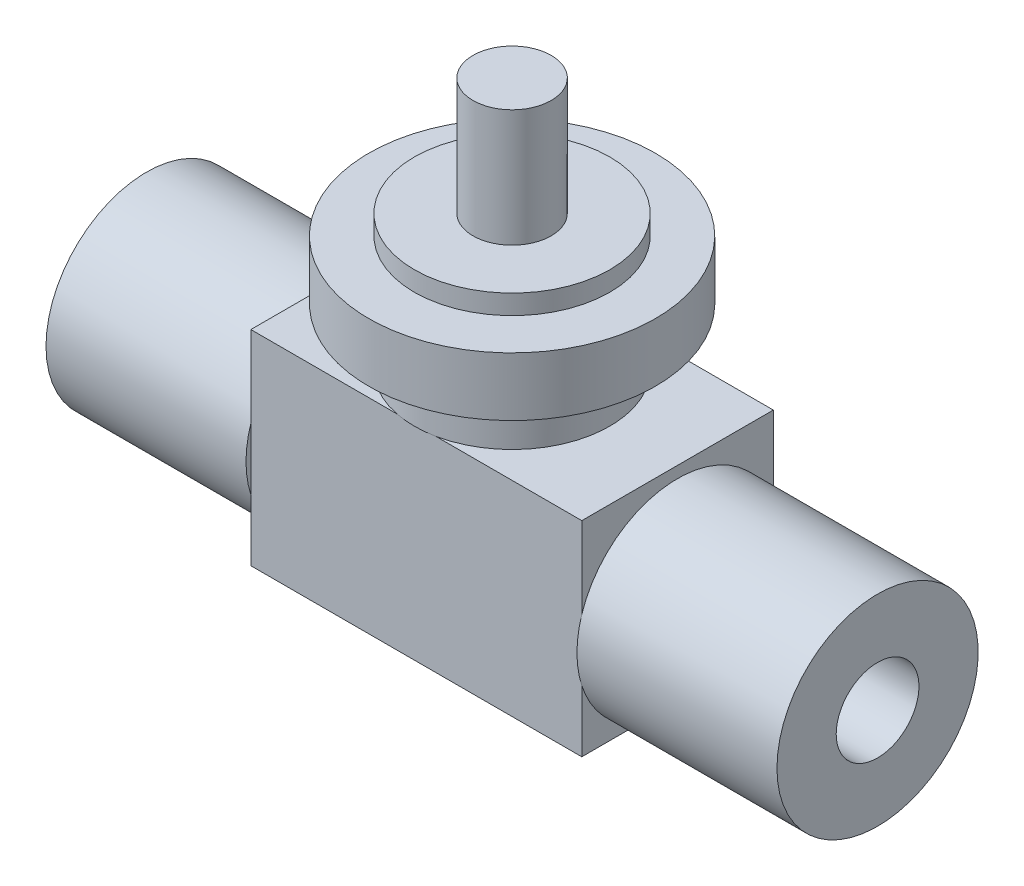
SolidWorks part; units mm, degrees
ref_plane "Front Plane" through (0, 0, 0) normal (0, 0, 1) x (1, 0, 0)
ref_plane "Top Plane" through (0, 0, 0) normal (0, 1, 0) x (1, 0, 0)
ref_plane "Right Plane" through (0, 0, 0) normal (1, 0, 0) x (0, 0, -1)
sketch "Body Sketch" plane through (0, 0, 0) normal (0, 0, 1) x (1, 0, 0)
  line L0 (-12.7, -7.1) -> (12.7, -7.1)
  line L1 (12.7, -7.1) -> (12.7, 8.6)
  line L2 (12.7, 8.6) -> (-12.7, 8.6)
  line L3 (-12.7, 8.6) -> (-12.7, -7.1)
extrude "Body" add sketch "Body Sketch" along normal mid plane 14.7
ref_axis "Engine Axis" through (30.855, 0, 0) along (-1, 0, 0)
ref_axis "Stem Axis" through (0, -9.5081, 0) along (0, 1, 0)
sketch "Nut +X Sketch" plane through (0, 0, 0) normal (0, 0, 1) x (1, 0, 0)
  line L0 (-1000, 0) -> (1000, 0) construction
  line L1 (12.7, 0) -> (28.05, 0)
  line L2 (28.05, 0) -> (28.05, 7.722)
  line L3 (28.05, 7.722) -> (12.7, 7.722)
  line L4 (12.7, 7.722) -> (12.7, 0)
revolve "Nut +X" add sketch "Nut +X Sketch" angle 360 about L0
sketch "Nut -X Sketch" plane through (0, 0, 0) normal (0, 0, 1) x (1, 0, 0)
  line L0 (-1000, 0) -> (1000, 0) construction
  line L1 (-28.05, 0) -> (-12.7, 0)
  line L2 (-12.7, 0) -> (-12.7, 7.722)
  line L3 (-12.7, 7.722) -> (-28.05, 7.722)
  line L4 (-28.05, 7.722) -> (-28.05, 0)
revolve "Nut -X" add sketch "Nut -X Sketch" angle 360 about L0
sketch "Socket +X Sketch" plane through (0, 0, 0) normal (0, 0, 1) x (1, 0, 0)
  line L0 (-1000, 0) -> (1000, 0) construction
  line L1 (12.85, 0) -> (29.05, 0)
  line L2 (29.05, 0) -> (29.05, 3.175)
  line L3 (29.05, 3.175) -> (12.85, 3.175)
  line L4 (12.85, 3.175) -> (12.85, 0)
revolve "Socket +X" cut sketch "Socket +X Sketch" angle 360 about L0
sketch "Socket -X Sketch" plane through (0, 0, 0) normal (0, 0, 1) x (1, 0, 0)
  line L0 (-1000, 0) -> (1000, 0) construction
  line L1 (-29.05, 0) -> (-12.85, 0)
  line L2 (-12.85, 0) -> (-12.85, 3.175)
  line L3 (-12.85, 3.175) -> (-29.05, 3.175)
  line L4 (-29.05, 3.175) -> (-29.05, 0)
revolve "Socket -X" cut sketch "Socket -X Sketch" angle 360 about L0
sketch "Stem Sketch" plane through (0, 0, 0) normal (0, 0, 1) x (1, 0, 0)
  line L0 (0, -500) -> (0, 500) construction
  line L1 (0, 8.6) -> (7.5, 8.6)
  line L2 (7.5, 8.6) -> (7.5, 13)
  line L3 (7.5, 13) -> (11, 13)
  line L4 (11, 13) -> (11, 17.5)
  line L5 (11, 17.5) -> (7.5, 17.5)
  line L6 (7.5, 17.5) -> (7.5, 19)
  line L7 (7.5, 19) -> (3, 19)
  line L8 (3, 19) -> (3, 28)
  line L9 (3, 28) -> (0, 28)
  line L10 (0, 28) -> (0, 8.6)
revolve "Stem" add sketch "Stem Sketch" angle 360 about L0
